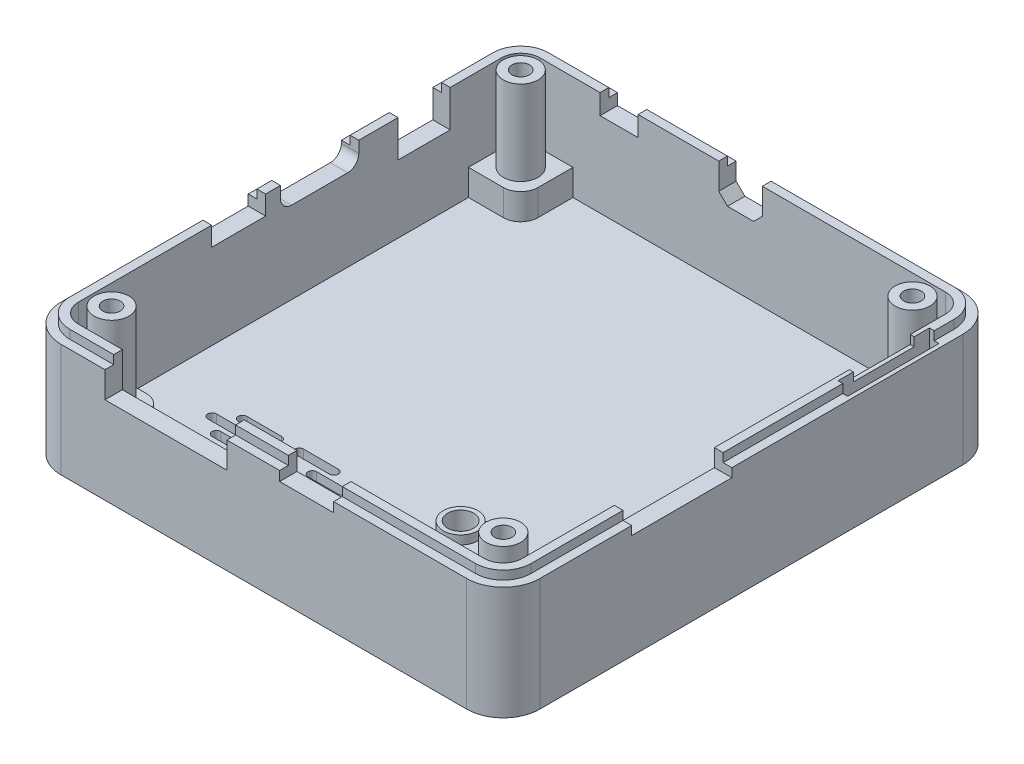
SolidWorks part; units mm, degrees
ref_plane "Front Plane" through (0, 0, 0) normal (0, 0, 1) x (1, 0, 0)
ref_plane "Top Plane" through (0, 0, 0) normal (0, 1, 0) x (1, 0, 0)
ref_plane "Right Plane" through (0, 0, 0) normal (1, 0, 0) x (0, 0, -1)
sketch "Sketch1" plane through (0, 0, 0) normal (0, 1, 0) x (1, 0, 0)
  line L17 (-23.3, 27.5) -> (23.3, 27.5)
  line L18 (-23.3, 26.5) -> (23.3, 26.5)
  line L26 (-25.5, 24.3) -> (-25.5, -24.3)
  line L27 (-23.3, -26.5) -> (23.3, -26.5)
  line L28 (25.5, 24.3) -> (25.5, -24.3)
  line L29 (-25.5, 26.5) -> (25.5, -26.5) construction
  line L30 (-25.5, -26.5) -> (25.5, 26.5) construction
  line L31 (26.5, 24.3) -> (26.5, -24.3)
  line L32 (-23.3, -27.5) -> (23.3, -27.5)
  line L33 (-26.5, 24.3) -> (-26.5, -24.3)
  line L34 (-23.3, 28.5) -> (23.3, 28.5)
  line L35 (27.5, 24.3) -> (27.5, -24.3)
  line L36 (-23.3, -28.5) -> (23.3, -28.5)
  line L37 (-27.5, 24.3) -> (-27.5, -24.3)
  line L38 (-19.5, 26.5) -> (-19.5, 22.5)
  line L39 (-25.5, -20.5) -> (-21.5, -20.5)
  line L40 (19.5, -26.5) -> (19.5, -22.5)
  line L41 (-25.5, 20.5) -> (-21.5, 20.5)
  line L42 (-19.5, -22.5) -> (-19.5, -26.5)
  line L43 (21.5, -20.5) -> (25.5, -20.5)
  line L44 (19.5, 22.5) -> (19.5, 26.5)
  line L45 (21.5, 20.5) -> (25.5, 20.5)
  arc A32 (25.5, -24.3) -> (23.3, -26.5) centre (23.3, -24.3) cw
  arc A33 (-23.3, -26.5) -> (-25.5, -24.3) centre (-23.3, -24.3) cw
  arc A34 (25.5, 24.3) -> (23.3, 26.5) centre (23.3, 24.3) ccw
  arc A35 (-23.3, 26.5) -> (-25.5, 24.3) centre (-23.3, 24.3) ccw
  arc A36 (26.5, 24.3) -> (23.3, 27.5) centre (23.3, 24.3) ccw
  arc A37 (26.5, -24.3) -> (23.3, -27.5) centre (23.3, -24.3) cw
  arc A38 (-23.3, -27.5) -> (-26.5, -24.3) centre (-23.3, -24.3) cw
  arc A39 (-23.3, 27.5) -> (-26.5, 24.3) centre (-23.3, 24.3) ccw
  arc A40 (27.5, 24.3) -> (23.3, 28.5) centre (23.3, 24.3) ccw
  arc A41 (27.5, -24.3) -> (23.3, -28.5) centre (23.3, -24.3) cw
  arc A42 (-23.3, -28.5) -> (-27.5, -24.3) centre (-23.3, -24.3) cw
  arc A43 (-23.3, 28.5) -> (-27.5, 24.3) centre (-23.3, 24.3) ccw
  circle A44 centre (-22.5, 23.5) radius 1
  circle A45 centre (22.5, 23.5) radius 1
  circle A46 centre (-22.5, -23.5) radius 1
  circle A47 centre (22.5, -23.5) radius 1
  arc A48 (19.5, 22.5) -> (21.5, 20.5) centre (21.5, 22.5) ccw
  arc A49 (21.5, -20.5) -> (19.5, -22.5) centre (21.5, -22.5) ccw
  arc A50 (-19.5, -22.5) -> (-21.5, -20.5) centre (-21.5, -22.5) ccw
  arc A51 (-19.5, 22.5) -> (-21.5, 20.5) centre (-21.5, 22.5) cw
  point P0 (0, 0)
  point P63 (19.5, 20.5)
  point P66 (19.5, -20.5)
  point P70 (-19.5, -20.5)
  point P73 (-19.5, 20.5)
  dimension "D3" = 2.2
  dimension "D14" = 3
  dimension "D17" = 3
  dimension "D18" = 2
  dimension "D19" = 2
  dimension "D28" = 6
  dimension "D10" = 3
  dimension "D11" = 3
  dimension "D12" = 3
  dimension "D13" = 3
  dimension "D15" = 3
  dimension "D16" = 3
  dimension "D20" = 2
  dimension "D21" = 2
  dimension "D30" = 2
  dimension "D1" = 51
  dimension "D2" = 53
  dimension "D4" = 1
  dimension "D5" = 1
  dimension "D6" = 53
  dimension "D7" = 55
  dimension "D8" = 55
  dimension "D9" = 57
  dimension "D22" = 6
  dimension "D23" = 6
  dimension "D24" = 6
  dimension "D25" = 6
  dimension "D26" = 6
  dimension "D27" = 6
  dimension "D29" = 6
extrude "Boss-Extrude1" add sketch "Sketch1" along normal blind 13 contours L34 A43 L37 A42 L36 A41 L35 A40 A39 L17 A36 L31 A37 L32 A38 L33 region at (0, 0, -27.7079)
extrude "Boss-Extrude2" add sketch "Sketch1<3>" along normal blind 14 contours L17 A39 L33 A38 L32 A37 L31 A36 A35 L18 A34 L28 A32 L27 A33 L26 region at (0, 0, -26.7362)
sketch "Sketch1<3>" plane through (0, 0, 0) normal (0, 1, 0) x (1, 0, 0) same geometry as "Sketch1"
extrude "Boss-Extrude3" add sketch "Sketch1<4>" along normal blind 2 contours L38 A51 L41 L26 L39 A50 L42 L27 L40 A49 L43 L28 L45 A48 L44 L18 region at (0, 0, 0)
sketch "Sketch1<4>" plane through (0, 0, 0) normal (0, 1, 0) x (1, 0, 0) same geometry as "Sketch1"
extrude "Boss-Extrude4" add sketch "Sketch1<5>" along normal blind 5 contours A51 L38 L18 A35 L26 L41 A44 | L42 A50 L39 L26 A33 L27 A46 | L43 A49 L40 L27 A32 L28 A47 | L44 A48 L45 L28 A34 L18 A45 region at (-21.4, 0, -26.4151) region at (21.4, 0, -26.4151) region at (-23.5, 0, 20.5849) region at (25.4151, 0, 22.4)
sketch "Sketch1<5>" plane through (0, 0, 0) normal (0, 1, 0) x (1, 0, 0) same geometry as "Sketch1"
sketch "Sketch2" plane through (0, 5, 0) normal (0, 1, 0) x (1, 0, 0)
  circle A0 centre (-22.5, 23.5) radius 1
  circle A1 centre (22.5, 23.5) radius 1
  circle A2 centre (22.5, -23.5) radius 1
  circle A3 centre (-22.5, -23.5) radius 1
  circle A4 centre (-22.5, -23.5) radius 2
  circle A5 centre (22.5, -23.5) radius 2
  circle A6 centre (22.5, 23.5) radius 2
  circle A7 centre (-22.5, 23.5) radius 2
  dimension "D1" = 2
  dimension "D2" = 4
  dimension "D3" = 2
  dimension "D4" = 4
  dimension "D5" = 2
  dimension "D6" = 4
  dimension "D7" = 2
  dimension "D8" = 4
extrude "Boss-Extrude5" add sketch "Sketch2" along normal blind 9.7
sketch "Sketch3" plane through (-27.5, 0, 0) normal (-1, 0, 0) x (0, 0, 1)
  line L0 (-24.3, 14) -> (24.3, 14) construction
  line L1 (-18.4, 14) -> (-12.4, 14)
  line L2 (-18.4, 14) -> (-18.4, 9.78)
  line L3 (-18.4, 9.78) -> (-12.4, 9.78)
  line L4 (-12.4, 14) -> (-12.4, 9.78)
  line L6 (-7.9, 14) -> (1.1, 14)
  line L7 (-7.9, 14) -> (-7.9, 12.68)
  line L8 (-6.62, 11.4) -> (-0.18, 11.4)
  line L9 (1.1, 14) -> (1.1, 12.68)
  line L10 (2.8, 14) -> (9, 14)
  line L11 (2.8, 14) -> (2.8, 11.8)
  line L12 (2.8, 11.8) -> (9, 11.8)
  line L13 (9, 14) -> (9, 11.8)
  line L14 (28.5, 13) -> (28.5, 0) construction
  line L15 (-28.5, 13) -> (-28.5, 0) construction
  arc A0 (1.1, 12.68) -> (-0.18, 11.4) centre (-0.18, 12.68) cw
  arc A1 (-6.62, 11.4) -> (-7.9, 12.68) centre (-6.62, 12.68) cw
  point P20 (1.1, 11.4)
  point P23 (-7.9, 11.4)
  dimension "D11" = 1.28
  dimension "D1" = 6
  dimension "D2" = 4.22
  dimension "D3" = 4.5
  dimension "D4" = 9
  dimension "D5" = 1.7
  dimension "D6" = 6.2
  dimension "D7" = 2.6
  dimension "D8" = 2.2
  dimension "D9" = 27.4
  dimension "D10" = 20.6
extrude "Cut-Extrude1" cut sketch "Sketch3" against normal blind 2
sketch "Sketch5" plane through (0, 0, -28.5) normal (0, 0, -1) x (-1, 0, 0)
  line L0 (0, 0) -> (0, 21.9509) construction
  line L1 (23.3, 14) -> (-23.3, 14) construction
  line L2 (1.75, 10) -> (-1.25, 10)
  line L3 (2.75, 11) -> (2.75, 14)
  line L4 (2.75, 14) -> (-2.25, 14)
  line L5 (-2.25, 11) -> (-2.25, 14)
  line L6 (2.75, 10) -> (-2.25, 14) construction
  line L7 (2.75, 14) -> (-2.25, 10) construction
  line L8 (-1.25, 10) -> (-2.25, 11)
  line L9 (2.75, 11) -> (1.75, 10)
  line L10 (27.5, 13) -> (27.5, 0) construction
  line L11 (12.02, 14) -> (16.38, 14)
  line L12 (12.02, 14) -> (12.02, 11.7)
  line L13 (12.02, 11.7) -> (16.38, 11.7)
  line L14 (16.38, 14) -> (16.38, 11.7)
  point P3 (0.25, 12)
  dimension "D1" = 0.25
  dimension "D2" = 4
  dimension "D3" = 5
  dimension "D4" = 2.3
  dimension "D5" = 4.36
  dimension "D6" = 11.12
extrude "Cut-Extrude3" cut sketch "Sketch5" against normal blind 2
sketch "Sketch6" plane through (0, 14, 0) normal (0, 1, 0) x (1, 0, 0)
  line L0 (21.5, 20.5) -> (25.5, 20.5) construction
  line L1 (25.95, 22) -> (27.05, 22)
  line L2 (25.95, 22) -> (25.95, 11.5)
  line L3 (25.95, 11.5) -> (27.05, 11.5)
  line L4 (27.05, 22) -> (27.05, 11.5)
  line L5 (25.5, 24.3) -> (25.5, -24.3) construction
  line L6 (27.5, 24.3) -> (27.5, -24.3) construction
  dimension "D1" = 1.5
  dimension "D2" = 10.5
  dimension "D3" = 1.1
  dimension "D4" = 0.45
  dimension "D5" = 0.45
extrude "Cut-Extrude4" cut sketch "Sketch6" against normal blind 3
sketch "Sketch7" plane through (27.5, 0, 0) normal (1, 0, 0) x (0, 0, -1)
  line L0 (22, 14) -> (11.5, 14) construction
  line L1 (13.25, 14) -> (20.25, 14)
  line L2 (13.25, 14) -> (13.25, 13)
  line L3 (13.25, 13) -> (20.25, 13)
  line L4 (20.25, 14) -> (20.25, 13)
  line L5 (28.5, 13) -> (28.5, 0) construction
  line L6 (11.5, 14) -> (-24.3, 14) construction
  line L7 (-13.75, 14) -> (-2.25, 14)
  line L8 (-13.75, 14) -> (-13.75, 12)
  line L9 (-13.75, 12) -> (-2.25, 12)
  line L10 (-2.25, 14) -> (-2.25, 12)
  line L11 (-28.5, 13) -> (-28.5, 0) construction
  dimension "D1" = 1
  dimension "D2" = 7
  dimension "D3" = 8.25
  dimension "D4" = 14.75
  dimension "D5" = 11.5
  dimension "D6" = 2
extrude "Cut-Extrude5" cut sketch "Sketch7" against normal blind 2
sketch "Sketch8" plane through (0, 0, 0) normal (0, -1, 0) x (1, 0, 0)
  circle A0 centre (-22.5, 23.5) radius 1
  circle A1 centre (22.5, 23.5) radius 1
  circle A2 centre (-22.5, -23.5) radius 1
  circle A3 centre (22.5, -23.5) radius 1
  dimension "D1" = 2
  dimension "D2" = 2
  dimension "D3" = 2
  dimension "D4" = 2
extrude "Boss-Extrude6" add sketch "Sketch8" against normal blind 2 separate body
sketch "Sketch9" plane through (0, 0, 28.5) normal (0, 0, 1) x (1, 0, 0)
  line L0 (-23.3, 14) -> (23.3, 14) construction
  line L1 (-18.25, 14) -> (-4.25, 14)
  line L2 (-18.25, 14) -> (-18.25, 10)
  line L3 (-18.25, 10) -> (-4.25, 10)
  line L4 (-4.25, 14) -> (-4.25, 10)
  line L5 (-27.5, 13) -> (-27.5, 0) construction
  line L6 (1.81, 14) -> (8.01, 14)
  line L7 (1.81, 14) -> (1.81, 11.9)
  line L8 (1.81, 11.9) -> (8.01, 11.9)
  line L9 (8.01, 14) -> (8.01, 11.9)
  point P10 (1.81, 12.95)
  dimension "D1" = 4
  dimension "D2" = 14
  dimension "D3" = 6.06
  dimension "D4" = 6.2
  dimension "D5" = 2.1
  dimension "D6" = 9.25
extrude "Cut-Extrude6" cut sketch "Sketch9" against normal blind 2
sketch "Sketch10" plane through (0, 0, 0) normal (0, -1, 0) x (1, 0, 0)
  line L0 (-23.3, 28.5) -> (23.3, 28.5) construction
  line L1 (27.5, -24.3) -> (27.5, 24.3) construction
  circle A0 centre (7.2, 17.6) radius 1.5
  circle A1 centre (7.2, 13.1) radius 1.5
  dimension "D1" = 3
  dimension "D2" = 3
  dimension "D3" = 4.5
  dimension "D4" = 10.9
  dimension "D5" = 20.3
  dimension "D6" = 15.4
extrude "Cut-Extrude7" cut sketch "Sketch10" against normal blind 2
sketch "Sketch11" plane through (0, 0, 0) normal (0, -1, 0) x (1, 0, 0)
  line L0 (-20.5381, 19) -> (-1.8375, 19) construction
  line L1 (-11.2, 23.9809) -> (-11.2, 13.932) construction
  line L3 (-23.3, 28.5) -> (23.3, 28.5) construction
  line L8 (-12.95, 19.5) -> (-9.45, 19.5)
  line L14 (-12.95, 18.5) -> (-9.45, 18.5)
  line L16 (-12.95, 19.5) -> (-9.45, 18.5) construction
  line L17 (-12.95, 18.5) -> (-9.45, 19.5) construction
  line L18 (-27.5, -24.3) -> (-27.5, 24.3) construction
  line L19 (-6.95, 19.5) -> (-3.45, 19.5)
  line L20 (-6.95, 18.5) -> (-3.45, 18.5)
  line L21 (-6.95, 19.5) -> (-3.45, 18.5) construction
  line L22 (-6.95, 18.5) -> (-3.45, 19.5) construction
  line L23 (-18.45, 19.5) -> (-14.95, 19.5)
  line L24 (-18.45, 18.5) -> (-14.95, 18.5)
  line L25 (-18.45, 19.5) -> (-14.95, 18.5) construction
  line L26 (-18.45, 18.5) -> (-14.95, 19.5) construction
  line L27 (-16.4532, 21) -> (-12.4532, 21)
  line L28 (-16.4532, 20) -> (-12.4532, 20)
  line L29 (-16.4532, 21) -> (-12.4532, 20) construction
  line L30 (-16.4532, 20) -> (-12.4532, 21) construction
  line L31 (-9.9532, 21) -> (-5.9532, 21)
  line L32 (-9.9532, 20) -> (-5.9532, 20)
  line L33 (-9.9532, 21) -> (-5.9532, 20) construction
  line L34 (-9.9532, 20) -> (-5.9532, 21) construction
  line L35 (-9.9532, 18) -> (-5.9532, 17) construction
  line L36 (-9.9532, 17) -> (-5.9532, 18) construction
  line L37 (-16.4532, 18) -> (-12.4532, 17) construction
  line L38 (-16.4532, 17) -> (-12.4532, 18) construction
  line L39 (-9.9532, 18) -> (-5.9532, 18)
  line L40 (-9.9532, 17) -> (-5.9532, 17)
  line L41 (-16.4532, 18) -> (-12.4532, 18)
  line L42 (-16.4532, 17) -> (-12.4532, 17)
  line L43 (-18.6354, 20.5) -> (-4.347, 20.5) construction
  line L44 (-19.0364, 17.5) -> (-3.4772, 17.5) construction
  line L45 (-18.45, 22.5) -> (-14.95, 21.5) construction
  line L46 (-18.45, 21.5) -> (-14.95, 22.5) construction
  line L47 (-6.95, 22.5) -> (-3.45, 21.5) construction
  line L48 (-6.95, 21.5) -> (-3.45, 22.5) construction
  line L49 (-12.95, 22.5) -> (-9.45, 21.5) construction
  line L50 (-12.95, 21.5) -> (-9.45, 22.5) construction
  line L51 (-18.45, 22.5) -> (-14.95, 22.5)
  line L52 (-18.45, 21.5) -> (-14.95, 21.5)
  line L53 (-6.95, 22.5) -> (-3.45, 22.5)
  line L54 (-6.95, 21.5) -> (-3.45, 21.5)
  line L55 (-12.95, 22.5) -> (-9.45, 22.5)
  line L56 (-12.95, 21.5) -> (-9.45, 21.5)
  line L57 (-18.45, 16.5) -> (-14.95, 15.5) construction
  line L58 (-18.45, 15.5) -> (-14.95, 16.5) construction
  line L59 (-6.95, 16.5) -> (-3.45, 15.5) construction
  line L60 (-6.95, 15.5) -> (-3.45, 16.5) construction
  line L61 (-12.95, 16.5) -> (-9.45, 15.5) construction
  line L62 (-12.95, 15.5) -> (-9.45, 16.5) construction
  line L63 (-18.45, 16.5) -> (-14.95, 16.5)
  line L64 (-18.45, 15.5) -> (-14.95, 15.5)
  line L65 (-6.95, 16.5) -> (-3.45, 16.5)
  line L66 (-6.95, 15.5) -> (-3.45, 15.5)
  line L67 (-12.95, 16.5) -> (-9.45, 16.5)
  line L68 (-12.95, 15.5) -> (-9.45, 15.5)
  line L69 (-20.9422, 22) -> (-1.06, 22) construction
  line L70 (-20.5381, 16) -> (-1.8375, 16) construction
  line L71 (-9.9532, 24) -> (-5.9532, 23) construction
  line L72 (-9.9532, 23) -> (-5.9532, 24) construction
  line L73 (-16.4532, 24) -> (-12.4532, 23) construction
  line L74 (-16.4532, 23) -> (-12.4532, 24) construction
  line L75 (-9.9532, 24) -> (-5.9532, 24)
  line L76 (-9.9532, 23) -> (-5.9532, 23)
  line L77 (-16.4532, 24) -> (-12.4532, 24)
  line L78 (-16.4532, 23) -> (-12.4532, 23)
  line L79 (-16.4532, 15) -> (-12.4532, 14) construction
  line L80 (-16.4532, 14) -> (-12.4532, 15) construction
  line L81 (-9.9532, 15) -> (-5.9532, 14) construction
  line L82 (-9.9532, 14) -> (-5.9532, 15) construction
  line L83 (-16.4532, 15) -> (-12.4532, 15)
  line L84 (-16.4532, 14) -> (-12.4532, 14)
  line L85 (-9.9532, 15) -> (-5.9532, 15)
  line L86 (-9.9532, 14) -> (-5.9532, 14)
  line L87 (-19.2, 23.5) -> (-3.6634, 23.5) construction
  line L88 (-12.95, 25.5) -> (-9.45, 24.5) construction
  line L89 (-12.95, 24.5) -> (-9.45, 25.5) construction
  line L90 (-6.95, 25.5) -> (-3.45, 24.5) construction
  line L91 (-6.95, 24.5) -> (-3.45, 25.5) construction
  line L92 (-18.45, 25.5) -> (-14.95, 24.5) construction
  line L93 (-18.45, 24.5) -> (-14.95, 25.5) construction
  line L94 (-12.95, 25.5) -> (-9.45, 25.5)
  line L95 (-12.95, 24.5) -> (-9.45, 24.5)
  line L96 (-6.95, 25.5) -> (-3.45, 25.5)
  line L97 (-6.95, 24.5) -> (-3.45, 24.5)
  line L98 (-18.45, 25.5) -> (-14.95, 25.5)
  line L99 (-18.45, 24.5) -> (-14.95, 24.5)
  arc A35 (-12.95, 19.5) -> (-12.95, 18.5) centre (-12.95, 19) ccw
  arc A36 (-9.45, 19.5) -> (-9.45, 18.5) centre (-9.45, 19) cw
  arc A37 (-6.95, 19.5) -> (-6.95, 18.5) centre (-6.95, 19) ccw
  arc A38 (-3.45, 19.5) -> (-3.45, 18.5) centre (-3.45, 19) cw
  arc A39 (-18.45, 19.5) -> (-18.45, 18.5) centre (-18.45, 19) ccw
  arc A40 (-14.95, 19.5) -> (-14.95, 18.5) centre (-14.95, 19) cw
  arc A41 (-16.4532, 21) -> (-16.4532, 20) centre (-16.4532, 20.5) ccw
  arc A42 (-12.4532, 21) -> (-12.4532, 20) centre (-12.4532, 20.5) cw
  arc A43 (-9.9532, 21) -> (-9.9532, 20) centre (-9.9532, 20.5) ccw
  arc A44 (-5.9532, 21) -> (-5.9532, 20) centre (-5.9532, 20.5) cw
  arc A45 (-5.9532, 17) -> (-5.9532, 18) centre (-5.9532, 17.5) ccw
  arc A46 (-9.9532, 17) -> (-9.9532, 18) centre (-9.9532, 17.5) cw
  arc A47 (-12.4532, 17) -> (-12.4532, 18) centre (-12.4532, 17.5) ccw
  arc A48 (-16.4532, 17) -> (-16.4532, 18) centre (-16.4532, 17.5) cw
  arc A49 (-14.95, 21.5) -> (-14.95, 22.5) centre (-14.95, 22) ccw
  arc A50 (-18.45, 21.5) -> (-18.45, 22.5) centre (-18.45, 22) cw
  arc A51 (-3.45, 21.5) -> (-3.45, 22.5) centre (-3.45, 22) ccw
  arc A52 (-6.95, 21.5) -> (-6.95, 22.5) centre (-6.95, 22) cw
  arc A53 (-9.45, 21.5) -> (-9.45, 22.5) centre (-9.45, 22) ccw
  arc A54 (-12.95, 21.5) -> (-12.95, 22.5) centre (-12.95, 22) cw
  arc A55 (-14.95, 15.5) -> (-14.95, 16.5) centre (-14.95, 16) ccw
  arc A56 (-18.45, 15.5) -> (-18.45, 16.5) centre (-18.45, 16) cw
  arc A57 (-3.45, 15.5) -> (-3.45, 16.5) centre (-3.45, 16) ccw
  arc A58 (-6.95, 15.5) -> (-6.95, 16.5) centre (-6.95, 16) cw
  arc A59 (-9.45, 15.5) -> (-9.45, 16.5) centre (-9.45, 16) ccw
  arc A60 (-12.95, 15.5) -> (-12.95, 16.5) centre (-12.95, 16) cw
  arc A61 (-5.9532, 23) -> (-5.9532, 24) centre (-5.9532, 23.5) ccw
  arc A62 (-9.9532, 23) -> (-9.9532, 24) centre (-9.9532, 23.5) cw
  arc A63 (-12.4532, 23) -> (-12.4532, 24) centre (-12.4532, 23.5) ccw
  arc A64 (-16.4532, 23) -> (-16.4532, 24) centre (-16.4532, 23.5) cw
  arc A65 (-16.4532, 15) -> (-16.4532, 14) centre (-16.4532, 14.5) ccw
  arc A66 (-12.4532, 15) -> (-12.4532, 14) centre (-12.4532, 14.5) cw
  arc A67 (-9.9532, 15) -> (-9.9532, 14) centre (-9.9532, 14.5) ccw
  arc A68 (-5.9532, 15) -> (-5.9532, 14) centre (-5.9532, 14.5) cw
  arc A69 (-12.95, 25.5) -> (-12.95, 24.5) centre (-12.95, 25) ccw
  arc A70 (-9.45, 25.5) -> (-9.45, 24.5) centre (-9.45, 25) cw
  arc A71 (-6.95, 25.5) -> (-6.95, 24.5) centre (-6.95, 25) ccw
  arc A72 (-3.45, 25.5) -> (-3.45, 24.5) centre (-3.45, 25) cw
  arc A73 (-18.45, 25.5) -> (-18.45, 24.5) centre (-18.45, 25) ccw
  arc A74 (-14.95, 25.5) -> (-14.95, 24.5) centre (-14.95, 25) cw
  point P0 (-11.2, 19)
  point P11 (-14.4532, 20.5)
  point P12 (-16.7, 19)
  point P13 (-5.2, 19)
  point P33 (-7.9532, 20.5)
  point P55 (-7.9532, 17.5)
  point P56 (-14.4532, 17.5)
  point P79 (-5.2, 22)
  point P80 (-16.7, 22)
  point P81 (-11.2, 22)
  point P100 (-5.2, 16)
  point P101 (-16.7, 16)
  point P102 (-11.2, 16)
  point P119 (-7.9532, 23.5)
  point P120 (-14.4532, 23.5)
  point P133 (-14.4532, 14.5)
  point P134 (-7.9532, 14.5)
  point P155 (-11.2, 25)
  point P156 (-16.7, 25)
  point P157 (-5.2, 25)
  dimension "D1" = 9.5
  dimension "D2" = 16.3
  dimension "D3" = 1
  dimension "D4" = 0.5
  dimension "D5" = 3.5
  dimension "D6" = 2
  dimension "D8" = 2
  dimension "D7" = 2
  dimension "D9" = 1
  dimension "D10" = 2
extrude "Cut-Extrude8" cut sketch "Sketch11" against normal blind 2
sketch "Sketch12" plane through (0, 2, 0) normal (0, 1, 0) x (1, 0, 0)
  circle A0 centre (7.2, -13.1) radius 1.5
  circle A1 centre (7.2, -13.1) radius 2
  circle A2 centre (7.2, -17.6) radius 1.5
  circle A3 centre (7.2, -17.6) radius 2
  dimension "D1" = 4
  dimension "D2" = 3
  dimension "D3" = 3
  dimension "D4" = 4
extrude "Boss-Extrude7" add sketch "Sketch12" along normal blind 1
